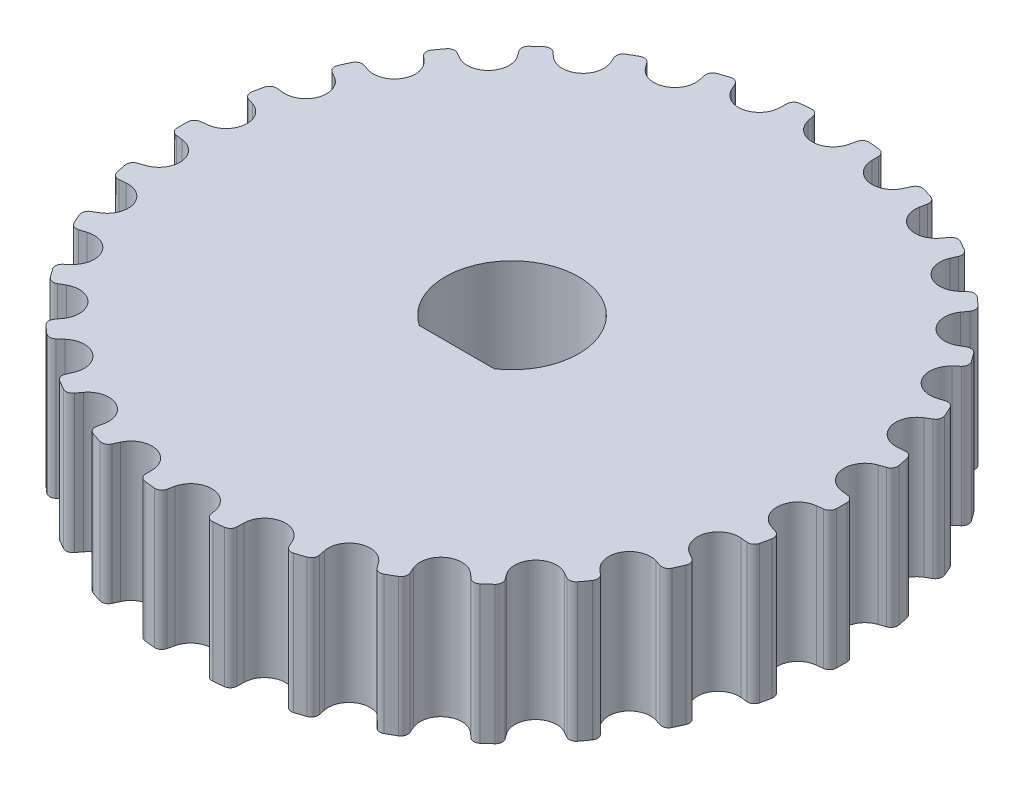
SolidWorks part; units mm, degrees
material "Acrylic (Medium-high impact)"
ref_plane "Front Plane" through (0, 0, 0) normal (0, 0, 1) x (1, 0, 0)
ref_plane "Top Plane" through (0, 0, 0) normal (0, 1, 0) x (1, 0, 0)
ref_plane "Right Plane" through (0, 0, 0) normal (1, 0, 0) x (0, 0, -1)
sketch "Sketch1" plane through (0, 0, 0) normal (0, 1, 0) x (1, 0, 0)
  circle A0 centre (0, 0) radius 14.3239
  dimension "D1" = 28.6479
extrude "Boss-Extrude1" add sketch "Sketch1" along normal blind 6
sketch "Sketch2" plane through (0, 6, 0) normal (0, 1, 0) x (1, 0, 0)
  line L0 (0, 0) -> (0, 14.3239) construction
  line L1 (-0.8883, 13.7564) -> (-0.95, 14.0339)
  line L2 (-2.9781, 14.0109) -> (-2.9781, 14.3239)
  line L3 (-2.9781, 14.3239) -> (2.9781, 14.3239)
  line L4 (0.8883, 13.7564) -> (0.95, 14.0339)
  line L5 (2.9781, 14.0109) -> (2.9781, 14.3239)
  circle A0 centre (0, 0) radius 14.3239 construction
  arc A1 (0.8883, 13.7564) -> (-0.8883, 13.7564) centre (0, 13.9539) cw
  arc A2 (-0.95, 14.0339) -> (-1.2694, 14.2676) centre (-1.2428, 13.9688) ccw
  arc A4 (0.95, 14.0339) -> (1.2694, 14.2676) centre (1.2428, 13.9688) cw
  arc A5 (-1.2694, 14.2676) -> (-2.9781, 14.0109) centre (0, 0) ccw
  arc A6 (1.2694, 14.2676) -> (2.9781, 14.0109) centre (0, 0) cw
  point P11 (0, 14.3239)
  point P19 (0, 13.0439)
  dimension "D3" = 0.3
  dimension "D5" = 0.91
  dimension "D2" = 0.95
  dimension "D4" = 1.28
  dimension "D6" = 12
extrude "Cut-Extrude1" cut sketch "Sketch2" against normal through all
pattern_circular "CirPattern1" count 30 over 360 about axis through (0, 6, 0) along (0, -1, 0) of "Cut-Extrude1"
sketch "Sketch3" plane through (0, 0, 0) normal (0, -1, 0) x (1, 0, 0)
  line L0 (1.6279, 2.4) -> (-1.6279, 2.4)
  arc A0 (-1.6279, 2.4) -> (1.6279, 2.4) centre (0, 0) ccw
  dimension "D1" = 5.8
  dimension "D2" = 2.4
extrude "Cut-Extrude2" cut sketch "Sketch3" against normal through all
sketch "Sketch5" plane through (0, 0, 0) normal (0, -1, 0) x (1, 0, 0)
  line L60 (6.3264, -12.2653) -> (6.4956, -12.4937)
  line L61 (7.5721, -11.8722) -> (7.4589, -11.6115)
  line L62 (8.7383, -10.682) -> (8.9513, -10.8702)
  line L63 (9.875, -10.0385) -> (9.7101, -9.807)
  line L64 (10.7682, -8.6318) -> (11.0157, -8.7716)
  line L65 (11.7463, -7.766) -> (11.5369, -7.5738)
  line L66 (12.3276, -6.2043) -> (12.5987, -6.2896)
  line L67 (13.1043, -5.1541) -> (12.8594, -5.0097)
  line L68 (13.3481, -3.5057) -> (13.6311, -3.5327)
  line L69 (13.8895, -2.3169) -> (13.62, -2.2266)
  line L70 (13.7853, -0.6538) -> (14.0677, -0.6215)
  line L71 (14.0677, 0.6215) -> (13.7853, 0.6538)
  line L72 (13.62, 2.2266) -> (13.8895, 2.3169)
  line L73 (13.6311, 3.5327) -> (13.3481, 3.5057)
  line L74 (12.8594, 5.0097) -> (13.1043, 5.1541)
  line L75 (12.5987, 6.2896) -> (12.3276, 6.2043)
  line L76 (11.5369, 7.5738) -> (11.7463, 7.766)
  line L77 (11.0157, 8.7716) -> (10.7682, 8.6318)
  line L78 (9.7101, 9.807) -> (9.875, 10.0385)
  line L79 (8.9513, 10.8702) -> (8.7383, 10.682)
  line L80 (7.4589, 11.6115) -> (7.5721, 11.8722)
  line L81 (6.4956, 12.4937) -> (6.3264, 12.2653)
  line L82 (4.8817, 12.9085) -> (4.9382, 13.1871)
  line L83 (3.7561, 13.5712) -> (3.638, 13.3126)
  line L84 (2.0912, 13.6414) -> (2.0886, 13.9257)
  line L85 (-0.8524, -14.0556) -> (-0.7907, -13.7781)
  line L86 (0.7907, -13.7781) -> (0.8524, -14.0556)
  line L87 (2.0886, -13.9257) -> (2.0912, -13.6414)
  line L88 (3.638, -13.3126) -> (3.7561, -13.5712)
  line L89 (4.9382, -13.1871) -> (4.8817, -12.9085)
  line L90 (6.3264, -12.2653) -> (6.4956, -12.4937)
  line L91 (7.5721, -11.8722) -> (7.4589, -11.6115)
  line L92 (8.7383, -10.682) -> (8.9513, -10.8702)
  line L93 (9.875, -10.0385) -> (9.7101, -9.807)
  line L94 (10.7682, -8.6318) -> (11.0157, -8.7716)
  line L95 (11.7463, -7.766) -> (11.5369, -7.5738)
  line L96 (12.3276, -6.2043) -> (12.5987, -6.2896)
  line L97 (13.1043, -5.1541) -> (12.8594, -5.0097)
  line L98 (13.3481, -3.5057) -> (13.6311, -3.5327)
  line L99 (13.8895, -2.3169) -> (13.62, -2.2266)
  line L100 (13.7853, -0.6538) -> (14.0677, -0.6215)
  line L101 (14.0677, 0.6215) -> (13.7853, 0.6538)
  line L102 (13.62, 2.2266) -> (13.8895, 2.3169)
  line L103 (13.6311, 3.5327) -> (13.3481, 3.5057)
  line L104 (12.8594, 5.0097) -> (13.1043, 5.1541)
  line L105 (12.5987, 6.2896) -> (12.3276, 6.2043)
  line L106 (11.5369, 7.5738) -> (11.7463, 7.766)
  line L107 (11.0157, 8.7716) -> (10.7682, 8.6318)
  line L108 (9.7101, 9.807) -> (9.875, 10.0385)
  line L109 (8.9513, 10.8702) -> (8.7383, 10.682)
  line L110 (7.4589, 11.6115) -> (7.5721, 11.8722)
  line L111 (6.4956, 12.4937) -> (6.3264, 12.2653)
  line L112 (4.8817, 12.9085) -> (4.9382, 13.1871)
  line L113 (3.7561, 13.5712) -> (3.638, 13.3126)
  line L114 (2.0912, 13.6414) -> (2.0886, 13.9257)
  line L115 (-0.8524, -14.0556) -> (-0.7907, -13.7781)
  line L116 (0.7907, -13.7781) -> (0.8524, -14.0556)
  line L117 (2.0886, -13.9257) -> (2.0912, -13.6414)
  line L118 (3.638, -13.3126) -> (3.7561, -13.5712)
  line L119 (4.9382, -13.1871) -> (4.8817, -12.9085)
  line L120 (0.8524, 14.0556) -> (0.7907, 13.7781)
  line L121 (0.8524, 14.0556) -> (0.7907, 13.7781)
  line L122 (-0.7907, 13.7781) -> (-0.8524, 14.0556)
  line L123 (-0.7907, 13.7781) -> (-0.8524, 14.0556)
  line L124 (-2.0886, 13.9257) -> (-2.0912, 13.6414)
  line L125 (-2.0886, 13.9257) -> (-2.0912, 13.6414)
  line L126 (-3.638, 13.3126) -> (-3.7561, 13.5712)
  line L127 (-3.638, 13.3126) -> (-3.7561, 13.5712)
  line L128 (-4.9382, 13.1871) -> (-4.8817, 12.9085)
  line L129 (-4.9382, 13.1871) -> (-4.8817, 12.9085)
  line L130 (-6.3264, 12.2653) -> (-6.4956, 12.4937)
  line L131 (-6.3264, 12.2653) -> (-6.4956, 12.4937)
  line L132 (-7.5721, 11.8722) -> (-7.4589, 11.6115)
  line L133 (-7.5721, 11.8722) -> (-7.4589, 11.6115)
  line L134 (-8.7383, 10.682) -> (-8.9513, 10.8702)
  line L135 (-8.7383, 10.682) -> (-8.9513, 10.8702)
  line L136 (-9.875, 10.0385) -> (-9.7101, 9.807)
  line L137 (-9.875, 10.0385) -> (-9.7101, 9.807)
  line L138 (-10.7682, 8.6318) -> (-11.0157, 8.7716)
  line L139 (-10.7682, 8.6318) -> (-11.0157, 8.7716)
  line L140 (-11.7463, 7.766) -> (-11.5369, 7.5738)
  line L141 (-11.7463, 7.766) -> (-11.5369, 7.5738)
  line L142 (-12.3276, 6.2043) -> (-12.5987, 6.2896)
  line L143 (-12.3276, 6.2043) -> (-12.5987, 6.2896)
  line L144 (-13.1043, 5.1541) -> (-12.8594, 5.0097)
  line L145 (-13.1043, 5.1541) -> (-12.8594, 5.0097)
  line L146 (-13.3481, 3.5057) -> (-13.6311, 3.5327)
  line L147 (-13.3481, 3.5057) -> (-13.6311, 3.5327)
  line L148 (-13.8895, 2.3169) -> (-13.62, 2.2266)
  line L149 (-13.8895, 2.3169) -> (-13.62, 2.2266)
  line L150 (-13.7853, 0.6538) -> (-14.0677, 0.6215)
  line L151 (-13.7853, 0.6538) -> (-14.0677, 0.6215)
  line L152 (-14.0677, -0.6215) -> (-13.7853, -0.6538)
  line L153 (-14.0677, -0.6215) -> (-13.7853, -0.6538)
  line L154 (-13.62, -2.2266) -> (-13.8895, -2.3169)
  line L155 (-13.62, -2.2266) -> (-13.8895, -2.3169)
  line L156 (-13.6311, -3.5327) -> (-13.3481, -3.5057)
  line L157 (-13.6311, -3.5327) -> (-13.3481, -3.5057)
  line L158 (-12.8594, -5.0097) -> (-13.1043, -5.1541)
  line L159 (-12.8594, -5.0097) -> (-13.1043, -5.1541)
  line L160 (-12.5987, -6.2896) -> (-12.3276, -6.2043)
  line L161 (-12.5987, -6.2896) -> (-12.3276, -6.2043)
  line L162 (-11.5369, -7.5738) -> (-11.7463, -7.766)
  line L163 (-11.5369, -7.5738) -> (-11.7463, -7.766)
  line L164 (-11.0157, -8.7716) -> (-10.7682, -8.6318)
  line L165 (-11.0157, -8.7716) -> (-10.7682, -8.6318)
  line L166 (-9.7101, -9.807) -> (-9.875, -10.0385)
  line L167 (-9.7101, -9.807) -> (-9.875, -10.0385)
  line L168 (-8.9513, -10.8702) -> (-8.7383, -10.682)
  line L169 (-8.9513, -10.8702) -> (-8.7383, -10.682)
  line L170 (-7.4589, -11.6115) -> (-7.5721, -11.8722)
  line L171 (-7.4589, -11.6115) -> (-7.5721, -11.8722)
  line L172 (-6.4956, -12.4937) -> (-6.3264, -12.2653)
  line L173 (-6.4956, -12.4937) -> (-6.3264, -12.2653)
  line L174 (-4.8817, -12.9085) -> (-4.9382, -13.1871)
  line L175 (-4.8817, -12.9085) -> (-4.9382, -13.1871)
  line L176 (-3.7561, -13.5712) -> (-3.638, -13.3126)
  line L177 (-3.7561, -13.5712) -> (-3.638, -13.3126)
  line L178 (-2.0912, -13.6414) -> (-2.0886, -13.9257)
  line L179 (-2.0912, -13.6414) -> (-2.0886, -13.9257)
  circle A60 centre (0, 0) radius 3.9038
  arc A120 (6.4956, -12.4937) -> (7.0114, -12.6052) centre (6.817, -12.2556) ccw
  arc A121 (7.0114, -12.6052) -> (7.4107, -12.3747) centre (0, 0) ccw
  arc A122 (7.4107, -12.3747) -> (7.5721, -11.8722) centre (7.2051, -12.0315) ccw
  arc A123 (8.7383, -10.682) -> (7.4589, -11.6115) centre (8.2019, -11.289) ccw
  arc A124 (8.9513, -10.8702) -> (9.479, -10.8719) centre (9.2161, -10.5704) ccw
  arc A125 (9.479, -10.8719) -> (9.8216, -10.5635) centre (0, 0) ccw
  arc A126 (9.8216, -10.5635) -> (9.875, -10.0385) centre (9.5492, -10.2705) ccw
  arc A127 (10.7682, -8.6318) -> (9.7101, -9.807) centre (10.3698, -9.337) ccw
  arc A128 (11.0157, -8.7716) -> (11.5323, -8.6636) centre (11.2124, -8.4233) ccw
  arc A129 (11.5323, -8.6636) -> (11.8032, -8.2906) centre (0, 0) ccw
  arc A130 (11.8032, -8.2906) -> (11.7463, -7.766) centre (11.4759, -8.0607) ccw
  arc A131 (12.3276, -6.2043) -> (11.5369, -7.5738) centre (12.0845, -6.977) ccw
  arc A132 (12.5987, -6.2896) -> (13.0815, -6.0766) centre (12.7187, -5.908) ccw
  arc A133 (13.0815, -6.0766) -> (13.269, -5.6554) centre (0, 0) ccw
  arc A134 (13.269, -5.6554) -> (13.1043, -5.1541) centre (12.901, -5.4986) ccw
  arc A135 (13.3481, -3.5057) -> (12.8594, -5.0097) centre (13.271, -4.312) ccw
  arc A136 (13.6311, -3.5327) -> (14.059, -3.224) centre (13.6691, -3.1346) ccw
  arc A137 (14.059, -3.224) -> (14.1549, -2.7731) centre (0, 0) ccw
  arc A138 (14.1549, -2.7731) -> (13.8895, -2.3169) centre (13.7623, -2.6962) ccw
  arc A139 (13.7853, -0.6538) -> (13.62, -2.2266) centre (13.8775, -1.4586) ccw
  arc A140 (14.0677, -0.6215) -> (14.4221, -0.2305) centre (14.0222, -0.2241) ccw
  arc A141 (14.4221, -0.2305) -> (14.4221, 0.2305) centre (0, 0) ccw
  arc A142 (14.4221, 0.2305) -> (14.0677, 0.6215) centre (14.0222, 0.2241) ccw
  arc A143 (13.62, 2.2266) -> (13.7853, 0.6538) centre (13.8775, 1.4586) ccw
  arc A144 (13.8895, 2.3169) -> (14.1549, 2.7731) centre (13.7623, 2.6962) ccw
  arc A145 (14.1549, 2.7731) -> (14.059, 3.224) centre (0, 0) ccw
  arc A146 (14.059, 3.224) -> (13.6311, 3.5327) centre (13.6691, 3.1346) ccw
  arc A147 (12.8594, 5.0097) -> (13.3481, 3.5057) centre (13.271, 4.312) ccw
  arc A148 (13.1043, 5.1541) -> (13.269, 5.6554) centre (12.901, 5.4986) ccw
  arc A149 (13.269, 5.6554) -> (13.0815, 6.0766) centre (0, 0) ccw
  arc A150 (13.0815, 6.0766) -> (12.5987, 6.2896) centre (12.7187, 5.908) ccw
  arc A151 (11.5369, 7.5738) -> (12.3276, 6.2043) centre (12.0845, 6.977) ccw
  arc A152 (11.7463, 7.766) -> (11.8032, 8.2906) centre (11.4759, 8.0607) ccw
  arc A153 (11.8032, 8.2906) -> (11.5323, 8.6636) centre (0, 0) ccw
  arc A154 (11.5323, 8.6636) -> (11.0157, 8.7716) centre (11.2124, 8.4233) ccw
  arc A155 (9.7101, 9.807) -> (10.7682, 8.6318) centre (10.3698, 9.337) ccw
  arc A156 (9.875, 10.0385) -> (9.8216, 10.5635) centre (9.5492, 10.2705) ccw
  arc A157 (9.8216, 10.5635) -> (9.479, 10.8719) centre (0, 0) ccw
  arc A158 (9.479, 10.8719) -> (8.9513, 10.8702) centre (9.2161, 10.5704) ccw
  arc A159 (7.4589, 11.6115) -> (8.7383, 10.682) centre (8.2019, 11.289) ccw
  arc A160 (7.5721, 11.8722) -> (7.4107, 12.3747) centre (7.2051, 12.0315) ccw
  arc A161 (7.4107, 12.3747) -> (7.0114, 12.6052) centre (0, 0) ccw
  arc A162 (7.0114, 12.6052) -> (6.4956, 12.4937) centre (6.817, 12.2556) ccw
  arc A163 (4.8817, 12.9085) -> (6.3264, 12.2653) centre (5.6756, 12.7476) ccw
  arc A164 (4.9382, 13.1871) -> (4.6759, 13.645) centre (4.5462, 13.2666) ccw
  arc A165 (4.6759, 13.645) -> (4.2375, 13.7875) centre (0, 0) ccw
  arc A166 (4.2375, 13.7875) -> (3.7561, 13.5712) centre (4.12, 13.4051) ccw
  arc A167 (2.0912, 13.6414) -> (3.638, 13.3126) centre (2.9012, 13.649) ccw
  arc A168 (2.0886, 13.9257) -> (1.7367, 14.319) centre (1.6886, 13.9219) ccw
  arc A169 (1.7367, 14.319) -> (1.2783, 14.3672) centre (0, 0) ccw
  arc A170 (-1.2783, -14.3672) -> (-0.8524, -14.0556) centre (-1.2428, -13.9688) ccw
  arc A171 (0.7907, -13.7781) -> (-0.7907, -13.7781) centre (0, -13.9539) ccw
  arc A172 (0.8524, -14.0556) -> (1.2783, -14.3672) centre (1.2428, -13.9688) ccw
  arc A173 (1.2783, -14.3672) -> (1.7367, -14.319) centre (0, 0) ccw
  arc A174 (1.7367, -14.319) -> (2.0886, -13.9257) centre (1.6886, -13.9219) ccw
  arc A175 (3.638, -13.3126) -> (2.0912, -13.6414) centre (2.9012, -13.649) ccw
  arc A176 (3.7561, -13.5712) -> (4.2375, -13.7875) centre (4.12, -13.4051) ccw
  arc A177 (4.2375, -13.7875) -> (4.6759, -13.645) centre (0, 0) ccw
  arc A178 (4.6759, -13.645) -> (4.9382, -13.1871) centre (4.5462, -13.2666) ccw
  arc A179 (6.3264, -12.2653) -> (4.8817, -12.9085) centre (5.6756, -12.7476) ccw
  arc A180 (6.4956, -12.4937) -> (7.0114, -12.6052) centre (6.817, -12.2556) ccw
  arc A181 (7.0114, -12.6052) -> (7.4107, -12.3747) centre (0, 0) ccw
  arc A182 (7.4107, -12.3747) -> (7.5721, -11.8722) centre (7.2051, -12.0315) ccw
  arc A183 (8.7383, -10.682) -> (7.4589, -11.6115) centre (8.2019, -11.289) ccw
  arc A184 (8.9513, -10.8702) -> (9.479, -10.8719) centre (9.2161, -10.5704) ccw
  arc A185 (9.479, -10.8719) -> (9.8216, -10.5635) centre (0, 0) ccw
  arc A186 (9.8216, -10.5635) -> (9.875, -10.0385) centre (9.5492, -10.2705) ccw
  arc A187 (10.7682, -8.6318) -> (9.7101, -9.807) centre (10.3698, -9.337) ccw
  arc A188 (11.0157, -8.7716) -> (11.5323, -8.6636) centre (11.2124, -8.4233) ccw
  arc A189 (11.5323, -8.6636) -> (11.8032, -8.2906) centre (0, 0) ccw
  arc A190 (11.8032, -8.2906) -> (11.7463, -7.766) centre (11.4759, -8.0607) ccw
  arc A191 (12.3276, -6.2043) -> (11.5369, -7.5738) centre (12.0845, -6.977) ccw
  arc A192 (12.5987, -6.2896) -> (13.0815, -6.0766) centre (12.7187, -5.908) ccw
  arc A193 (13.0815, -6.0766) -> (13.269, -5.6554) centre (0, 0) ccw
  arc A194 (13.269, -5.6554) -> (13.1043, -5.1541) centre (12.901, -5.4986) ccw
  arc A195 (13.3481, -3.5057) -> (12.8594, -5.0097) centre (13.271, -4.312) ccw
  arc A196 (13.6311, -3.5327) -> (14.059, -3.224) centre (13.6691, -3.1346) ccw
  arc A197 (14.059, -3.224) -> (14.1549, -2.7731) centre (0, 0) ccw
  arc A198 (14.1549, -2.7731) -> (13.8895, -2.3169) centre (13.7623, -2.6962) ccw
  arc A199 (13.7853, -0.6538) -> (13.62, -2.2266) centre (13.8775, -1.4586) ccw
  arc A200 (14.0677, -0.6215) -> (14.4221, -0.2305) centre (14.0222, -0.2241) ccw
  arc A201 (14.4221, -0.2305) -> (14.4221, 0.2305) centre (0, 0) ccw
  arc A202 (14.4221, 0.2305) -> (14.0677, 0.6215) centre (14.0222, 0.2241) ccw
  arc A203 (13.62, 2.2266) -> (13.7853, 0.6538) centre (13.8775, 1.4586) ccw
  arc A204 (13.8895, 2.3169) -> (14.1549, 2.7731) centre (13.7623, 2.6962) ccw
  arc A205 (14.1549, 2.7731) -> (14.059, 3.224) centre (0, 0) ccw
  arc A206 (14.059, 3.224) -> (13.6311, 3.5327) centre (13.6691, 3.1346) ccw
  arc A207 (12.8594, 5.0097) -> (13.3481, 3.5057) centre (13.271, 4.312) ccw
  arc A208 (13.1043, 5.1541) -> (13.269, 5.6554) centre (12.901, 5.4986) ccw
  arc A209 (13.269, 5.6554) -> (13.0815, 6.0766) centre (0, 0) ccw
  arc A210 (13.0815, 6.0766) -> (12.5987, 6.2896) centre (12.7187, 5.908) ccw
  arc A211 (11.5369, 7.5738) -> (12.3276, 6.2043) centre (12.0845, 6.977) ccw
  arc A212 (11.7463, 7.766) -> (11.8032, 8.2906) centre (11.4759, 8.0607) ccw
  arc A213 (11.8032, 8.2906) -> (11.5323, 8.6636) centre (0, 0) ccw
  arc A214 (11.5323, 8.6636) -> (11.0157, 8.7716) centre (11.2124, 8.4233) ccw
  arc A215 (9.7101, 9.807) -> (10.7682, 8.6318) centre (10.3698, 9.337) ccw
  arc A216 (9.875, 10.0385) -> (9.8216, 10.5635) centre (9.5492, 10.2705) ccw
  arc A217 (9.8216, 10.5635) -> (9.479, 10.8719) centre (0, 0) ccw
  arc A218 (9.479, 10.8719) -> (8.9513, 10.8702) centre (9.2161, 10.5704) ccw
  arc A219 (7.4589, 11.6115) -> (8.7383, 10.682) centre (8.2019, 11.289) ccw
  arc A220 (7.5721, 11.8722) -> (7.4107, 12.3747) centre (7.2051, 12.0315) ccw
  arc A221 (7.4107, 12.3747) -> (7.0114, 12.6052) centre (0, 0) ccw
  arc A222 (7.0114, 12.6052) -> (6.4956, 12.4937) centre (6.817, 12.2556) ccw
  arc A223 (4.8817, 12.9085) -> (6.3264, 12.2653) centre (5.6756, 12.7476) ccw
  arc A224 (4.9382, 13.1871) -> (4.6759, 13.645) centre (4.5462, 13.2666) ccw
  arc A225 (4.6759, 13.645) -> (4.2375, 13.7875) centre (0, 0) ccw
  arc A226 (4.2375, 13.7875) -> (3.7561, 13.5712) centre (4.12, 13.4051) ccw
  arc A227 (2.0912, 13.6414) -> (3.638, 13.3126) centre (2.9012, 13.649) ccw
  arc A228 (2.0886, 13.9257) -> (1.7367, 14.319) centre (1.6886, 13.9219) ccw
  arc A229 (1.7367, 14.319) -> (1.2783, 14.3672) centre (0, 0) ccw
  arc A230 (-1.2783, -14.3672) -> (-0.8524, -14.0556) centre (-1.2428, -13.9688) ccw
  arc A231 (0.7907, -13.7781) -> (-0.7907, -13.7781) centre (0, -13.9539) ccw
  arc A232 (0.8524, -14.0556) -> (1.2783, -14.3672) centre (1.2428, -13.9688) ccw
  arc A233 (1.2783, -14.3672) -> (1.7367, -14.319) centre (0, 0) ccw
  arc A234 (1.7367, -14.319) -> (2.0886, -13.9257) centre (1.6886, -13.9219) ccw
  arc A235 (3.638, -13.3126) -> (2.0912, -13.6414) centre (2.9012, -13.649) ccw
  arc A236 (3.7561, -13.5712) -> (4.2375, -13.7875) centre (4.12, -13.4051) ccw
  arc A237 (4.2375, -13.7875) -> (4.6759, -13.645) centre (0, 0) ccw
  arc A238 (4.6759, -13.645) -> (4.9382, -13.1871) centre (4.5462, -13.2666) ccw
  arc A239 (6.3264, -12.2653) -> (4.8817, -12.9085) centre (5.6756, -12.7476) ccw
  arc A241 (1.2783, 14.3672) -> (0.8524, 14.0556) centre (1.2428, 13.9688) ccw
  arc A242 (1.2783, 14.3672) -> (0.8524, 14.0556) centre (1.2428, 13.9688) ccw
  arc A243 (-0.7907, 13.7781) -> (0.7907, 13.7781) centre (0, 13.9539) ccw
  arc A244 (-0.7907, 13.7781) -> (0.7907, 13.7781) centre (0, 13.9539) ccw
  arc A245 (-0.8524, 14.0556) -> (-1.2783, 14.3672) centre (-1.2428, 13.9688) ccw
  arc A246 (-0.8524, 14.0556) -> (-1.2783, 14.3672) centre (-1.2428, 13.9688) ccw
  arc A247 (-1.2783, 14.3672) -> (-1.7367, 14.319) centre (0, 0) ccw
  arc A248 (-1.2783, 14.3672) -> (-1.7367, 14.319) centre (0, 0) ccw
  arc A249 (-1.7367, 14.319) -> (-2.0886, 13.9257) centre (-1.6886, 13.9219) ccw
  arc A250 (-1.7367, 14.319) -> (-2.0886, 13.9257) centre (-1.6886, 13.9219) ccw
  arc A251 (-3.638, 13.3126) -> (-2.0912, 13.6414) centre (-2.9012, 13.649) ccw
  arc A252 (-3.638, 13.3126) -> (-2.0912, 13.6414) centre (-2.9012, 13.649) ccw
  arc A253 (-3.7561, 13.5712) -> (-4.2375, 13.7875) centre (-4.12, 13.4051) ccw
  arc A254 (-3.7561, 13.5712) -> (-4.2375, 13.7875) centre (-4.12, 13.4051) ccw
  arc A255 (-4.2375, 13.7875) -> (-4.6759, 13.645) centre (0, 0) ccw
  arc A256 (-4.2375, 13.7875) -> (-4.6759, 13.645) centre (0, 0) ccw
  arc A257 (-4.6759, 13.645) -> (-4.9382, 13.1871) centre (-4.5462, 13.2666) ccw
  arc A258 (-4.6759, 13.645) -> (-4.9382, 13.1871) centre (-4.5462, 13.2666) ccw
  arc A259 (-6.3264, 12.2653) -> (-4.8817, 12.9085) centre (-5.6756, 12.7476) ccw
  arc A260 (-6.3264, 12.2653) -> (-4.8817, 12.9085) centre (-5.6756, 12.7476) ccw
  arc A261 (-6.4956, 12.4937) -> (-7.0114, 12.6052) centre (-6.817, 12.2556) ccw
  arc A262 (-6.4956, 12.4937) -> (-7.0114, 12.6052) centre (-6.817, 12.2556) ccw
  arc A263 (-7.0114, 12.6052) -> (-7.4107, 12.3747) centre (0, 0) ccw
  arc A264 (-7.0114, 12.6052) -> (-7.4107, 12.3747) centre (0, 0) ccw
  arc A265 (-7.4107, 12.3747) -> (-7.5721, 11.8722) centre (-7.2051, 12.0315) ccw
  arc A266 (-7.4107, 12.3747) -> (-7.5721, 11.8722) centre (-7.2051, 12.0315) ccw
  arc A267 (-8.7383, 10.682) -> (-7.4589, 11.6115) centre (-8.2019, 11.289) ccw
  arc A268 (-8.7383, 10.682) -> (-7.4589, 11.6115) centre (-8.2019, 11.289) ccw
  arc A269 (-8.9513, 10.8702) -> (-9.479, 10.8719) centre (-9.2161, 10.5704) ccw
  arc A270 (-8.9513, 10.8702) -> (-9.479, 10.8719) centre (-9.2161, 10.5704) ccw
  arc A271 (-9.479, 10.8719) -> (-9.8216, 10.5635) centre (0, 0) ccw
  arc A272 (-9.479, 10.8719) -> (-9.8216, 10.5635) centre (0, 0) ccw
  arc A273 (-9.8216, 10.5635) -> (-9.875, 10.0385) centre (-9.5492, 10.2705) ccw
  arc A274 (-9.8216, 10.5635) -> (-9.875, 10.0385) centre (-9.5492, 10.2705) ccw
  arc A275 (-10.7682, 8.6318) -> (-9.7101, 9.807) centre (-10.3698, 9.337) ccw
  arc A276 (-10.7682, 8.6318) -> (-9.7101, 9.807) centre (-10.3698, 9.337) ccw
  arc A277 (-11.0157, 8.7716) -> (-11.5323, 8.6636) centre (-11.2124, 8.4233) ccw
  arc A278 (-11.0157, 8.7716) -> (-11.5323, 8.6636) centre (-11.2124, 8.4233) ccw
  arc A279 (-11.5323, 8.6636) -> (-11.8032, 8.2906) centre (0, 0) ccw
  arc A280 (-11.5323, 8.6636) -> (-11.8032, 8.2906) centre (0, 0) ccw
  arc A281 (-11.8032, 8.2906) -> (-11.7463, 7.766) centre (-11.4759, 8.0607) ccw
  arc A282 (-11.8032, 8.2906) -> (-11.7463, 7.766) centre (-11.4759, 8.0607) ccw
  arc A283 (-12.3276, 6.2043) -> (-11.5369, 7.5738) centre (-12.0845, 6.977) ccw
  arc A284 (-12.3276, 6.2043) -> (-11.5369, 7.5738) centre (-12.0845, 6.977) ccw
  arc A285 (-12.5987, 6.2896) -> (-13.0815, 6.0766) centre (-12.7187, 5.908) ccw
  arc A286 (-12.5987, 6.2896) -> (-13.0815, 6.0766) centre (-12.7187, 5.908) ccw
  arc A287 (-13.0815, 6.0766) -> (-13.269, 5.6554) centre (0, 0) ccw
  arc A288 (-13.0815, 6.0766) -> (-13.269, 5.6554) centre (0, 0) ccw
  arc A289 (-13.269, 5.6554) -> (-13.1043, 5.1541) centre (-12.901, 5.4986) ccw
  arc A290 (-13.269, 5.6554) -> (-13.1043, 5.1541) centre (-12.901, 5.4986) ccw
  arc A291 (-13.3481, 3.5057) -> (-12.8594, 5.0097) centre (-13.271, 4.312) ccw
  arc A292 (-13.3481, 3.5057) -> (-12.8594, 5.0097) centre (-13.271, 4.312) ccw
  arc A293 (-13.6311, 3.5327) -> (-14.059, 3.224) centre (-13.6691, 3.1346) ccw
  arc A294 (-13.6311, 3.5327) -> (-14.059, 3.224) centre (-13.6691, 3.1346) ccw
  arc A295 (-14.059, 3.224) -> (-14.1549, 2.7731) centre (0, 0) ccw
  arc A296 (-14.059, 3.224) -> (-14.1549, 2.7731) centre (0, 0) ccw
  arc A297 (-14.1549, 2.7731) -> (-13.8895, 2.3169) centre (-13.7623, 2.6962) ccw
  arc A298 (-14.1549, 2.7731) -> (-13.8895, 2.3169) centre (-13.7623, 2.6962) ccw
  arc A299 (-13.7853, 0.6538) -> (-13.62, 2.2266) centre (-13.8775, 1.4586) ccw
  arc A300 (-13.7853, 0.6538) -> (-13.62, 2.2266) centre (-13.8775, 1.4586) ccw
  arc A301 (-14.0677, 0.6215) -> (-14.4221, 0.2305) centre (-14.0222, 0.2241) ccw
  arc A302 (-14.0677, 0.6215) -> (-14.4221, 0.2305) centre (-14.0222, 0.2241) ccw
  arc A303 (-14.4221, 0.2305) -> (-14.4221, -0.2305) centre (0, 0) ccw
  arc A304 (-14.4221, 0.2305) -> (-14.4221, -0.2305) centre (0, 0) ccw
  arc A305 (-14.4221, -0.2305) -> (-14.0677, -0.6215) centre (-14.0222, -0.2241) ccw
  arc A306 (-14.4221, -0.2305) -> (-14.0677, -0.6215) centre (-14.0222, -0.2241) ccw
  arc A307 (-13.62, -2.2266) -> (-13.7853, -0.6538) centre (-13.8775, -1.4586) ccw
  arc A308 (-13.62, -2.2266) -> (-13.7853, -0.6538) centre (-13.8775, -1.4586) ccw
  arc A309 (-13.8895, -2.3169) -> (-14.1549, -2.7731) centre (-13.7623, -2.6962) ccw
  arc A310 (-13.8895, -2.3169) -> (-14.1549, -2.7731) centre (-13.7623, -2.6962) ccw
  arc A311 (-14.1549, -2.7731) -> (-14.059, -3.224) centre (0, 0) ccw
  arc A312 (-14.1549, -2.7731) -> (-14.059, -3.224) centre (0, 0) ccw
  arc A313 (-14.059, -3.224) -> (-13.6311, -3.5327) centre (-13.6691, -3.1346) ccw
  arc A314 (-14.059, -3.224) -> (-13.6311, -3.5327) centre (-13.6691, -3.1346) ccw
  arc A315 (-12.8594, -5.0097) -> (-13.3481, -3.5057) centre (-13.271, -4.312) ccw
  arc A316 (-12.8594, -5.0097) -> (-13.3481, -3.5057) centre (-13.271, -4.312) ccw
  arc A317 (-13.1043, -5.1541) -> (-13.269, -5.6554) centre (-12.901, -5.4986) ccw
  arc A318 (-13.1043, -5.1541) -> (-13.269, -5.6554) centre (-12.901, -5.4986) ccw
  arc A319 (-13.269, -5.6554) -> (-13.0815, -6.0766) centre (0, 0) ccw
  arc A320 (-13.269, -5.6554) -> (-13.0815, -6.0766) centre (0, 0) ccw
  arc A321 (-13.0815, -6.0766) -> (-12.5987, -6.2896) centre (-12.7187, -5.908) ccw
  arc A322 (-13.0815, -6.0766) -> (-12.5987, -6.2896) centre (-12.7187, -5.908) ccw
  arc A323 (-11.5369, -7.5738) -> (-12.3276, -6.2043) centre (-12.0845, -6.977) ccw
  arc A324 (-11.5369, -7.5738) -> (-12.3276, -6.2043) centre (-12.0845, -6.977) ccw
  arc A325 (-11.7463, -7.766) -> (-11.8032, -8.2906) centre (-11.4759, -8.0607) ccw
  arc A326 (-11.7463, -7.766) -> (-11.8032, -8.2906) centre (-11.4759, -8.0607) ccw
  arc A327 (-11.8032, -8.2906) -> (-11.5323, -8.6636) centre (0, 0) ccw
  arc A328 (-11.8032, -8.2906) -> (-11.5323, -8.6636) centre (0, 0) ccw
  arc A329 (-11.5323, -8.6636) -> (-11.0157, -8.7716) centre (-11.2124, -8.4233) ccw
  arc A330 (-11.5323, -8.6636) -> (-11.0157, -8.7716) centre (-11.2124, -8.4233) ccw
  arc A331 (-9.7101, -9.807) -> (-10.7682, -8.6318) centre (-10.3698, -9.337) ccw
  arc A332 (-9.7101, -9.807) -> (-10.7682, -8.6318) centre (-10.3698, -9.337) ccw
  arc A333 (-9.875, -10.0385) -> (-9.8216, -10.5635) centre (-9.5492, -10.2705) ccw
  arc A334 (-9.875, -10.0385) -> (-9.8216, -10.5635) centre (-9.5492, -10.2705) ccw
  arc A335 (-9.8216, -10.5635) -> (-9.479, -10.8719) centre (0, 0) ccw
  arc A336 (-9.8216, -10.5635) -> (-9.479, -10.8719) centre (0, 0) ccw
  arc A337 (-9.479, -10.8719) -> (-8.9513, -10.8702) centre (-9.2161, -10.5704) ccw
  arc A338 (-9.479, -10.8719) -> (-8.9513, -10.8702) centre (-9.2161, -10.5704) ccw
  arc A339 (-7.4589, -11.6115) -> (-8.7383, -10.682) centre (-8.2019, -11.289) ccw
  arc A340 (-7.4589, -11.6115) -> (-8.7383, -10.682) centre (-8.2019, -11.289) ccw
  arc A341 (-7.5721, -11.8722) -> (-7.4107, -12.3747) centre (-7.2051, -12.0315) ccw
  arc A342 (-7.5721, -11.8722) -> (-7.4107, -12.3747) centre (-7.2051, -12.0315) ccw
  arc A343 (-7.4107, -12.3747) -> (-7.0114, -12.6052) centre (0, 0) ccw
  arc A344 (-7.4107, -12.3747) -> (-7.0114, -12.6052) centre (0, 0) ccw
  arc A345 (-7.0114, -12.6052) -> (-6.4956, -12.4937) centre (-6.817, -12.2556) ccw
  arc A346 (-7.0114, -12.6052) -> (-6.4956, -12.4937) centre (-6.817, -12.2556) ccw
  arc A347 (-4.8817, -12.9085) -> (-6.3264, -12.2653) centre (-5.6756, -12.7476) ccw
  arc A348 (-4.8817, -12.9085) -> (-6.3264, -12.2653) centre (-5.6756, -12.7476) ccw
  arc A349 (-4.9382, -13.1871) -> (-4.6759, -13.645) centre (-4.5462, -13.2666) ccw
  arc A350 (-4.9382, -13.1871) -> (-4.6759, -13.645) centre (-4.5462, -13.2666) ccw
  arc A351 (-4.6759, -13.645) -> (-4.2375, -13.7875) centre (0, 0) ccw
  arc A352 (-4.6759, -13.645) -> (-4.2375, -13.7875) centre (0, 0) ccw
  arc A353 (-4.2375, -13.7875) -> (-3.7561, -13.5712) centre (-4.12, -13.4051) ccw
  arc A354 (-4.2375, -13.7875) -> (-3.7561, -13.5712) centre (-4.12, -13.4051) ccw
  arc A355 (-2.0912, -13.6414) -> (-3.638, -13.3126) centre (-2.9012, -13.649) ccw
  arc A356 (-2.0912, -13.6414) -> (-3.638, -13.3126) centre (-2.9012, -13.649) ccw
  arc A357 (-2.0886, -13.9257) -> (-1.7367, -14.319) centre (-1.6886, -13.9219) ccw
  arc A358 (-2.0886, -13.9257) -> (-1.7367, -14.319) centre (-1.6886, -13.9219) ccw
  arc A359 (-1.7367, -14.319) -> (-1.2783, -14.3672) centre (0, 0) ccw
  arc A360 (-1.7367, -14.319) -> (-1.2783, -14.3672) centre (0, 0) ccw
  dimension "D1" = 0.1
extrude "Boss-Extrude2" [suppressed] add sketch "Sketch5" against normal up to surface (5.8 mm away) up to face at (0, 6, -0.25)
sketch "Sketch6" plane through (0, 6, 0) normal (0, 1, 0) x (1, 0, 0)
  circle A0 centre (0, -10) radius 2.5
  dimension "D1" = 5
  dimension "D2" = 10
extrude "Cut-Extrude3" [suppressed] cut sketch "Sketch6" against normal through all
equation "\"smallPulleyTeeth\"= 30"
equation "\"largePulleyTeeth\"= 30"
equation "\"eighthThick\"= 3.0mm"
equation "\"D1@Sketch1\"=3*\"smallPulleyTeeth\"/pi"
equation "\"D1@Boss-Extrude1\" = \"eighthThick\" * 2"
equation "\"D6@Sketch2\"=360/\"smallPulleyTeeth\""
equation "\"quarterThick\"=6.0mm"
equation "\"D1@CirPattern1\"=\"smallPulleyTeeth\""
equation "\"sixteenthThick\"= 1.7mm"
equation "\"OD\"= 145mm"
equation "\"puckAngle\"= 60.5deg"
equation "\"puckDiam\"= 76.5mm"
equation "\"axlePress\"= 5.9mm"
equation "\"press\"= 0.2mm"
equation "\"wheelClear\"= 0.3mm"
equation "\"10-32clear\"= 4.8mm"
equation "\"6-32clear\"= 3.3mm"
equation "\"8-32clear\"= 4.0mm"
equation "\"wheelHeight\"= 22mm"
equation "\"D1@Sketch3\"=\"axlePress\"-0.1"
